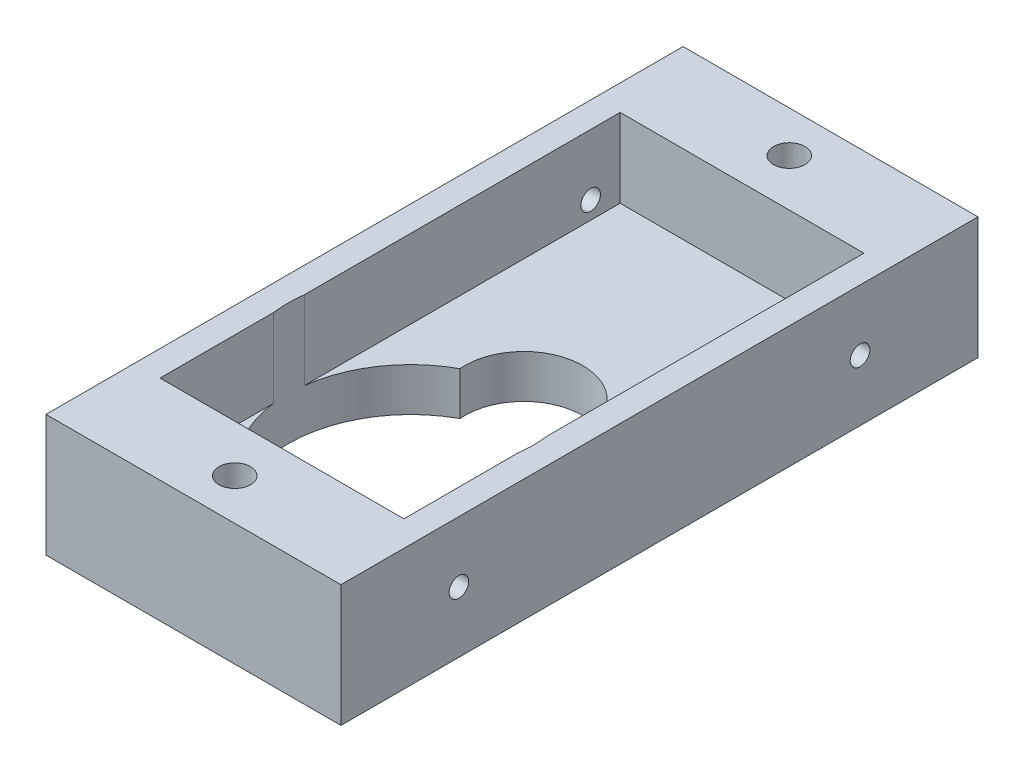
SolidWorks part; units mm, degrees
ref_plane "前视基准面" through (0, 0, 0) normal (0, 0, 1) x (1, 0, 0)
ref_plane "上视基准面" through (0, 0, 0) normal (0, 1, 0) x (1, 0, 0)
ref_plane "右视基准面" through (0, 0, 0) normal (1, 0, 0) x (0, 0, -1)
other "Configuration Table"
sketch "草图1" plane through (0, 0, 0) normal (0, 1, 0) x (1, 0, 0)
  line L1 (0, 0) -> (15, 0)
  line L2 (0, 0) -> (0, -32.4)
  line L3 (0, -32.4) -> (15, -32.4)
  line L4 (15, 0) -> (15, -32.4)
  circle A4 centre (3, -3) radius 0.8
  circle A5 centre (12, -3) radius 0.8
  circle A6 centre (3, -29.4) radius 0.8
  circle A7 centre (12, -29.4) radius 0.8
  circle A8 centre (7.5, -21.35) radius 6.25
  circle A9 centre (7.5, -15.6) radius 3
  point P10 (7.5, -32.4)
  dimension "D3" = 1.6
  dimension "D6" = 12.5
  dimension "D7" = 6
  dimension "D1" = 3
  dimension "D2" = 15
  dimension "D4" = 11.05
  dimension "D5" = 5.75
  dimension "D9" = 3
  dimension "D10" = 3
  dimension "D11" = 3
  dimension "32.4" = 32.4
extrude "凸台-拉伸1" add sketch "草图1" along normal blind 2.2 contours L2 L3 L4 L1 | A7 | A6 | A4 | A5
extrude "切除-拉伸1" cut sketch "草图1<3>" along normal through all contours A9 | A8
sketch "草图1<3>" plane through (0, 0, 0) normal (0, 1, 0) x (1, 0, 0) same geometry as "草图1"
sketch "草图2" plane through (0, 2.2, 0) normal (0, 1, 0) x (1, 0, 0)
  line L0 (0, 0) -> (0, -32.4) construction
  line L1 (15, -32.4) -> (0, -32.4)
  line L2 (15, -32.4) -> (15, -27.9)
  line L3 (15, -27.9) -> (0, -27.9)
  line L4 (0, -32.4) -> (0, -27.9)
  line L6 (15, 0) -> (0, 0)
  line L7 (15, 0) -> (15, -4.5)
  line L8 (15, -4.5) -> (0, -4.5)
  line L9 (0, 0) -> (0, -4.5)
  line L10 (15, -32.4) -> (13.7, -32.4)
  line L11 (15, -32.4) -> (15, 0)
  line L12 (15, 0) -> (13.7, 0)
  line L13 (13.7, -32.4) -> (13.7, 0)
  line L15 (0, 0) -> (1.3, 0)
  line L16 (0, 0) -> (0, -32.4)
  line L17 (0, -32.4) -> (1.3, -32.4)
  line L18 (1.3, 0) -> (1.3, -32.4)
  arc M18 (10.4886, -15.8609) -> (4.5114, -15.8609) centre (7.5, -21.35) cw
  line M19 (15, 0) -> (0, 0)
  line M20 (0, 0) -> (0, -32.4)
  line M21 (0, -32.4) -> (15, -32.4)
  line M22 (15, -32.4) -> (15, 0)
  circle M23 centre (12, -29.4) radius 0.8
  circle M24 centre (3, -29.4) radius 0.8
  circle M25 centre (3, -3) radius 0.8
  circle M26 centre (12, -3) radius 0.8
  dimension "D1" = 4.5
  dimension "D2" = 1.3
  dimension "D3" = 1.3
extrude "凸台-拉伸2" add sketch "草图2" along normal blind 4 contours L6 L18 L8 L13 M25 M26 | L18 L8 M19 M20 | L13 L8 M22 M19 | L3 L18 L1 L13 M24 M23 | L18 L3 M20 M21 | L13 L1 L3 M22 | M25 | M26 | M24 | M23 | L13 L3 L8 M22 M18 | L18 L8 L3 M20 M18 region at (14.35, 2.2, 30.15) region at (7.5, 2.2, 30.2082) region at (14.3511, 2.2, 16.1911) region at (0.65, 2.2, 30.15) region at (14.35, 2.2, 2.25) region at (0.6489, 2.2, 16.1911) region at (7.5, 2.2, 2.1918) region at (0.65, 2.2, 2.25) region at (12, 2.2, 29.4) region at (3, 2.2, 29.4) region at (3, 2.2, 3) region at (12, 2.2, 3)
sketch "草图3" plane through (0, 6.2, 0) normal (0, 1, 0) x (1, 0, 0)
  line L1 (15, 0) -> (0, 0) construction
  line L2 (0, -32.4) -> (15, -32.4) construction
  circle A0 centre (7.5, -30.3) radius 0.8
  circle A1 centre (7.5, -2.1) radius 0.8
  point P11 (7.5, -32.4)
  dimension "D1" = 1.6
  dimension "D2" = 2.1
  dimension "D3" = 2.1
extrude "切除-拉伸2" cut sketch "草图3" against normal blind 3 contours A1 | A0
sketch "草图4" plane through (0, 0, 0) normal (-1, 0, 0) x (0, 0, 1)
  line L0 (0, 6.2) -> (0, 0) construction
  line L1 (6, 3.1) -> (0, 3.1) construction
  line L2 (26.4, 3.1) -> (32.4, 3.1) construction
  line L3 (32.4, 6.2) -> (32.4, 0) construction
  circle A0 centre (6, 3.1) radius 0.5
  circle A1 centre (26.4, 3.1) radius 0.5
  point P6 (0, 3.1)
  dimension "D1" = 1
  dimension "D2" = 6
extrude "切除-拉伸3" cut sketch "草图4" against normal through all contours A1 | A0
